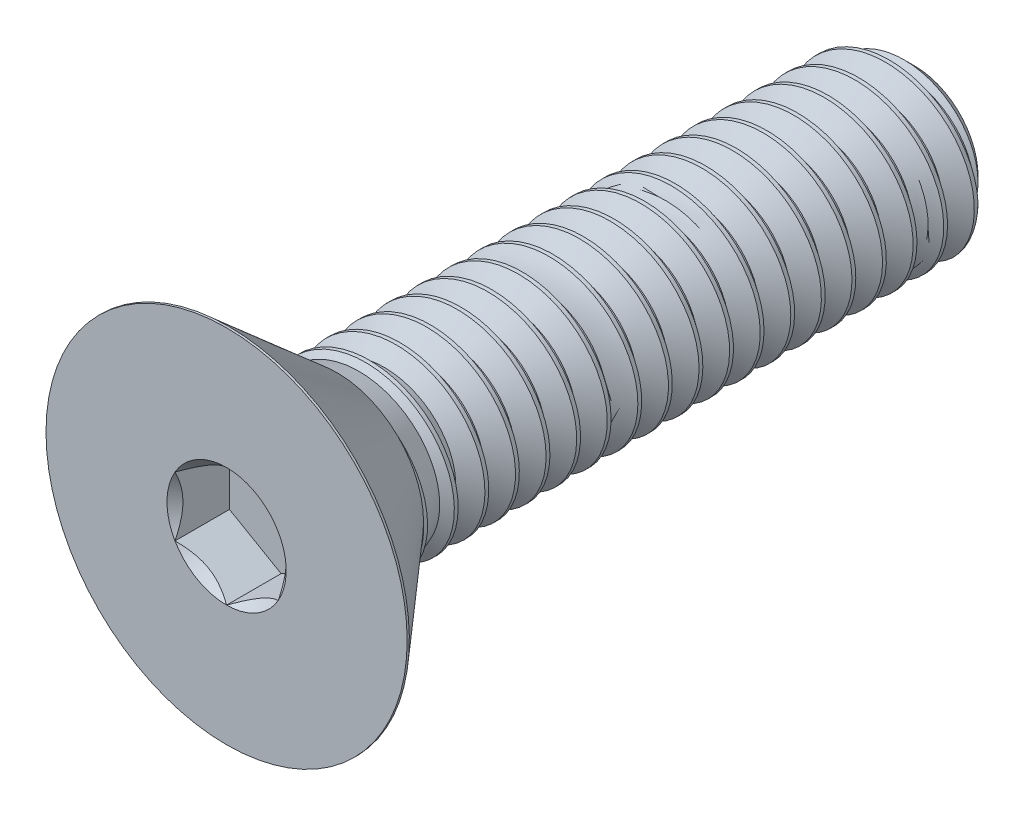
SolidWorks part; units mm, degrees
ref_plane "Front Plane" through (0, 0, 0) normal (0, 0, 1) x (1, 0, 0)
ref_plane "Top Plane" through (0, 0, 0) normal (0, 1, 0) x (1, 0, 0)
ref_plane "Right Plane" through (0, 0, 0) normal (1, 0, 0) x (0, 0, -1)
sketch "Sketch1" plane through (0, 0, 0) normal (1, 0, 0) x (0, 0, -1)
  line L0 (-15.875, 0) -> (15.875, 0) construction
  line L1 (-15.875, 0) -> (-15.875, 8.3312)
  line L2 (-15.875, 8.3312) -> (-15.7744, 8.3312)
  line L3 (-15.7744, 8.3312) -> (-10.8458, 4.0468)
  line L4 (-15.7744, -8.3312) -> (-10.8458, -4.0468)
  line L5 (15.875, 0) -> (15.875, 3.9751)
  line L6 (15.875, 3.9751) -> (-10.8458, 3.9751)
  line L7 (14.8167, 3.9751) -> (15.875, 2.9168)
  line L8 (15.7868, 4.1279) -> (16.4924, 2.9058) construction
  line L9 (16.4924, 2.9058) -> (17.1979, 4.1279) construction
  line L10 (17.1979, 4.1279) -> (15.7868, 4.1279) construction
  line L11 (15.8309, 4.0515) -> (17.1538, 4.0515)
  line L12 (17.1538, 4.0515) -> (16.5806, 3.0586)
  line L13 (16.5806, 3.0586) -> (16.4042, 3.0586)
  line L14 (16.4042, 3.0586) -> (15.8309, 4.0515)
  line L15 (16.4924, 3.0586) -> (16.4924, 2.9058) construction
  line L16 (15.875, 3.9751) -> (17.1097, 3.9751) construction
  line L17 (16.4924, 4.1279) -> (16.4924, 3.9751) construction
  line L18 (15.875, -3.9751) -> (-10.8458, -3.9751)
  arc A0 (-10.8458, 4.0468) -> (-10.654, 3.9751) centre (-10.654, 4.2675) ccw
  point P2 (0, 0)
  point P23 (-13.3604, 0)
  point P27 (16.4924, 4.0515)
  point P30 (13.7583, -3.9751)
  point P31 (-10.8458, 8.3312)
  point P33 (-10.8458, -8.3312)
  point P34 (-15.7744, -8.3312)
  point P35 (-15.875, 8.3312)
  dimension "Length" = 31.75
  dimension "Head Height" = 5.0292
  dimension "Head Diameter" = 16.6624
  dimension "Countersink Angle" = 82
  dimension "Screw Size Decimal Equivalent" = 7.9502
  dimension "Pitch" = 1.4111
  dimension "D4" = 0.1764
  dimension "D3" = 45
  dimension "D5" = 1.0583
  dimension "D6" = 2.5146
  dimension "D1" = 2.1167
  dimension "D7" = 0.1006
sketch "Sketch8" plane through (0, 0, 0) normal (0, 0, 1) x (1, 0, 0)
  line L1 (0, 2.7496) -> (-2.3812, 1.3748)
  line L2 (-2.3812, 1.3748) -> (-2.3812, -1.3748)
  line L3 (-2.3812, -1.3748) -> (0, -2.7496)
  line L4 (0, -2.7496) -> (2.3812, -1.3748)
  line L5 (2.3812, -1.3748) -> (2.3812, 1.3748)
  line L6 (2.3812, 1.3748) -> (0, 2.7496)
  circle A0 centre (0, 0) radius 2.3812 construction
  dimension "Drive Size" = 4.7625
sketch "Sketch2" plane through (0, 0, 0) normal (1, 0, 0) x (0, 0, -1)
  line L0 (-15.7744, 8.3312) -> (-10.8458, 4.0468) construction
  line L1 (-15.875, 0) -> (-15.875, 8.3312) construction
  line L2 (-15.7744, 8.3312) -> (-10.7633, 3.9751)
  line L3 (-15.875, 0) -> (-15.875, 8.3312)
  line L4 (-15.875, 8.3312) -> (-15.7744, 8.3312) construction
  line L5 (-15.875, 8.3312) -> (-15.7744, 8.3312)
  line L6 (-10.7633, 3.9751) -> (14.8167, 3.9751)
  line L7 (14.8167, 3.9751) -> (15.875, 2.9168)
  line L8 (15.875, 2.9168) -> (15.875, 0)
  line L9 (15.875, 0) -> (-15.875, 0)
revolve "Revolve1" add sketch "Sketch2" angle 360 about L9
sketch "Sketch9" plane through (0, 0, 15.875) normal (0, 0, 1) x (1, 0, 0)
  line L0 (2.3812, -1.3748) -> (2.3812, 1.3748) construction
  line L1 (0, -2.7496) -> (2.3812, -1.3748) construction
  line L2 (-2.3812, -1.3748) -> (0, -2.7496) construction
  line L3 (-2.3812, 1.3748) -> (-2.3812, -1.3748) construction
  line L4 (0, 2.7496) -> (-2.3812, 1.3748) construction
  line L5 (2.3812, 1.3748) -> (0, 2.7496) construction
  line L6 (2.3812, -1.3748) -> (2.3812, 1.3748)
  line L7 (0, -2.7496) -> (2.3812, -1.3748)
  line L8 (-2.3812, -1.3748) -> (0, -2.7496)
  line L9 (-2.3812, 1.3748) -> (-2.3812, -1.3748)
  line L10 (0, 2.7496) -> (-2.3812, 1.3748)
  line L11 (2.3812, 1.3748) -> (0, 2.7496)
sketch "Sketch10" plane through (0, 0, 15.875) normal (0, 0, 1) x (1, 0, 0)
  circle A0 centre (0, 0) radius 2.7496
extrude "Cut-Extrude2" cut sketch "Sketch10" against normal up to vertex (2.5146 mm away) draft 45 up to point (0, 0, 13.3604)
extrude "Cut-Extrude1" cut sketch "Sketch9" against normal up to vertex (2.5146 mm away) up to point (0, 0, 13.3604)
ref_plane "Plane1" through (0, 0, 10.7633) normal (0, 0, 1) x (1, 0, 0)
split "Split1" trim tools "Plane1" bodies to split 111 resulting bodies 105 106
sketch "Sketch3" plane through (0, 0, -15.875) normal (0, 0, -1) x (-1, 0, 0)
  circle A0 centre (0, 0) radius 3.9751 construction
  circle A1 centre (0, 0) radius 3.9751
curve "Helix/Spiral1" pitch 1.4111 height 31.75 radius 3.9751 centre (0, 0, -15.875) axis (0, 0, 1) start towards (0, 1, 0)
sketch "Sketch4" plane through (0, 0, 0) normal (1, 0, 0) x (0, 0, -1)
  line L0 (15.8309, 4.0515) -> (17.1538, 4.0515) construction
  line L1 (16.4042, 3.0586) -> (15.8309, 4.0515) construction
  line L2 (16.5806, 3.0586) -> (16.4042, 3.0586) construction
  line L3 (17.1538, 4.0515) -> (16.5806, 3.0586) construction
  line L4 (15.8309, 4.0515) -> (17.1538, 4.0515)
  line L5 (16.4042, 3.0586) -> (15.8309, 4.0515)
  line L6 (16.5806, 3.0586) -> (16.4042, 3.0586)
  line L7 (17.1538, 4.0515) -> (16.5806, 3.0586)
sweep "Cut-Sweep1" cut profiles "Sketch4" path "Helix/Spiral1" align with end faces yes
sketch "Sketch7" plane through (0, 0, 10.7633) normal (0, 0, 1) x (1, 0, 0)
  circle A0 centre (0, 0) radius 3.9751
extrude "Boss-Extrude2" add sketch "Sketch7" against normal up to next (26.6383 mm away) draft 20
equation "\"D4@Sketch1\" = \"Pitch@Sketch1\" / 8"
equation "\"D5@Sketch1\"=\"Pitch@Sketch1\"*0.75"
equation "\"D4@Helix/Spiral1\"=\"Pitch@Sketch1\""
equation "\"D3@Helix/Spiral1\"=\"Length@Sketch1\""
equation "\"D6@Sketch1\"=\"Head Height@Sketch1\"/2"
equation "\"D1@Sketch1\"=\"Pitch@Sketch1\"*1.5"
equation "\"D7@Sketch1\"=\"Head Height@Sketch1\"*0.02"
